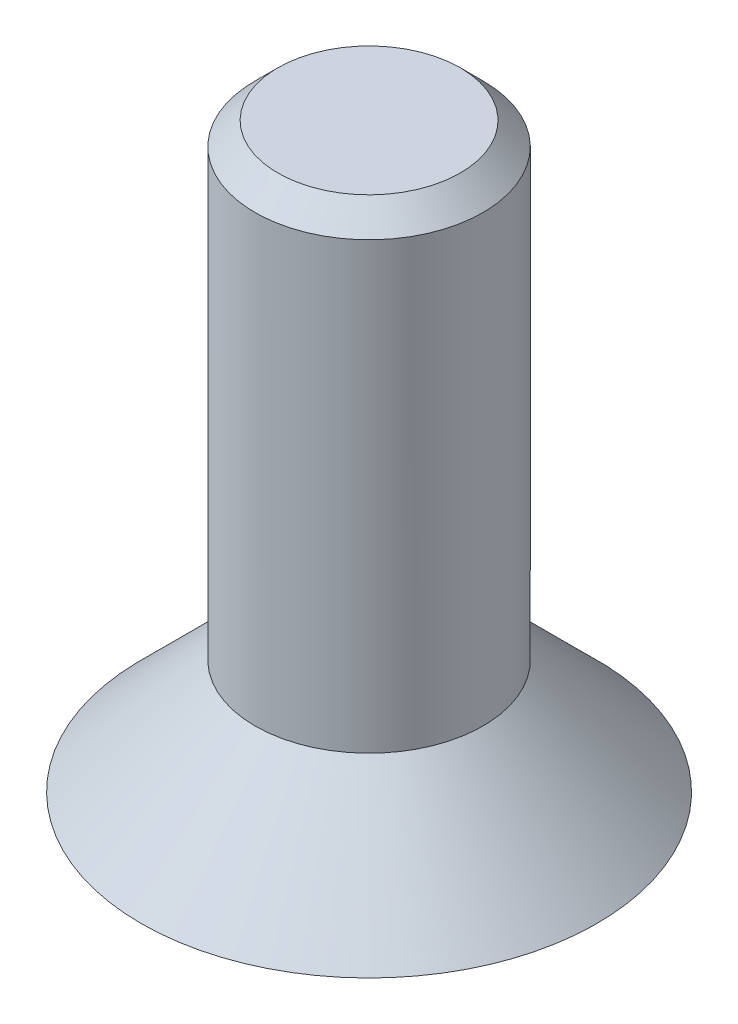
SolidWorks part; units mm, degrees
material "铸造合金钢"
ref_plane "前视基准面" through (0, 0, 0) normal (0, 0, 1) x (1, 0, 0)
ref_plane "上视基准面" through (0, 0, 0) normal (0, 1, 0) x (1, 0, 0)
ref_plane "右视基准面" through (0, 0, 0) normal (1, 0, 0) x (0, 0, -1)
sketch "草图1" plane through (0, 0, 0) normal (0, 1, 0) x (1, 0, 0)
  line L1 (0, -0.866) -> (0.75, -0.433)
  line L2 (0.75, -0.433) -> (0.75, 0.433)
  line L3 (0.75, 0.433) -> (0, 0.866)
  line L4 (0, 0.866) -> (-0.75, 0.433)
  line L5 (-0.75, 0.433) -> (-0.75, -0.433)
  line L6 (-0.75, -0.433) -> (0, -0.866)
  circle A0 centre (0, 0) radius 2
  circle A1 centre (0, 0) radius 0.75 construction
  dimension "D1" = 4
  dimension "D2" = 1.5
extrude "凸台-拉伸1" add sketch "草图1" along normal blind 1
chamfer "倒角1" distance 1 angle 45 1 edges at (0, 1, 2)
sketch "草图2" plane through (0, 1, 0) normal (0, 1, 0) x (1, 0, 0)
  circle A0 centre (0, 0) radius 1
  dimension "D1" = 2
extrude "凸台-拉伸2" add sketch "草图2" along normal blind 4.1
chamfer "倒角2" distance 0.2 angle 45 1 edges at (0, 5.1, 1)
